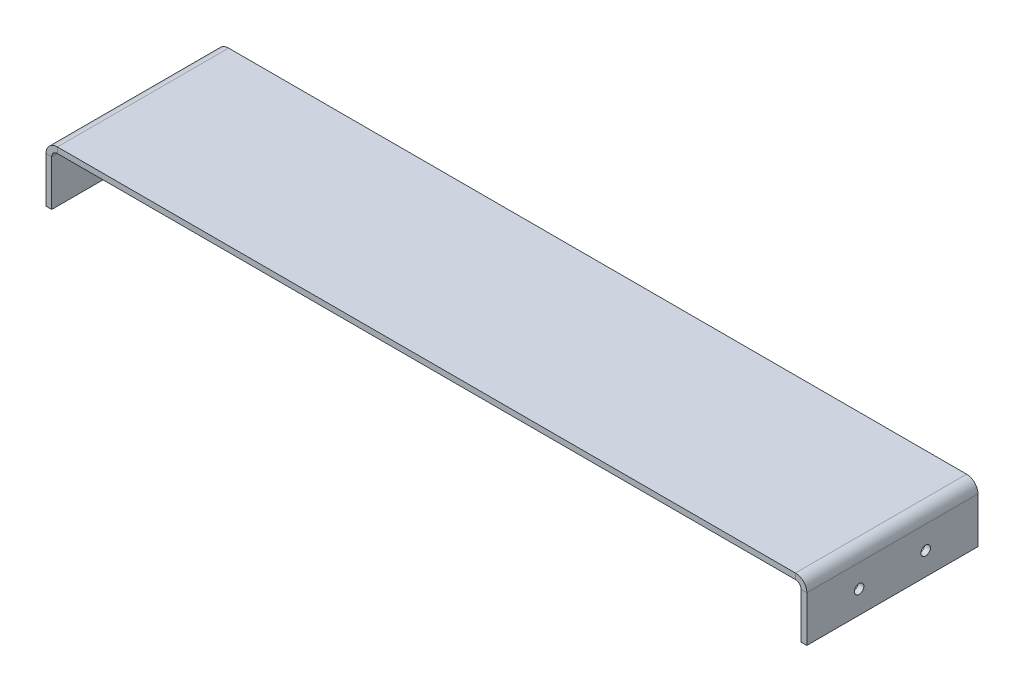
SolidWorks part; units mm, degrees
note: The reader was unsure of these and kept them because the rebuilt part matched: thickness of "Base-Flange1", "Edge-Flange1", "Sheet-Metal2", "Sheet-Metal3", "Sheet-Metal4"; flange length of "Edge-Flange1".
material "Wrought Stainless Steel"
ref_plane "Front Plane" through (0, 0, 0) normal (0, 0, 1) x (1, 0, 0)
ref_plane "Top Plane" through (0, 0, 0) normal (0, 1, 0) x (1, 0, 0)
ref_plane "Right Plane" through (0, 0, 0) normal (1, 0, 0) x (0, 0, -1)
sketch "Sketch1" plane through (0, 0, 0) normal (0, 1, 0) x (1, 0, 0)
  line L0 (0, -1000) -> (0, 49000) construction
  line L1 (-1000, 0) -> (-200, 0) construction
  line L4 (-200, 0) -> (-200, 90)
  line L5 (-200, 90) -> (200, 90)
  line L6 (200, 0) -> (200, 90)
  line L10 (200, 0) -> (49000, 0) construction
  line L11 (-200, 0) -> (200, 0)
  point P16 (0, 23.33)
  dimension "D2" = 90
  dimension "D3" = 400
base flange "Base-Flange1" sketch "Sketch1" thickness 3 reverse thickness direction no parameters "D1"=1
edge flange "Edge-Flange1" sketch "Sketch10" flange profiles "Sketch10", "Sketch11" flange angle 90 flange length 30 flange position material inside bend radius 3 thickness 3 relief obround parameters "D6"=10, "D8"=0.2
sketch "Sketch10" plane through (-200, -3, 0) normal (-1, 0, 0) x (0, 0, -1)
  line L0 (90, 0) -> (0, 0) construction
  line L1 (90, 0) -> (0, 0)
  line L2 (0, 0) -> (0, 27)
  line L3 (0, 27) -> (90, 27)
  line L4 (90, 27) -> (90, 0)
sketch "Sketch11" plane through (200, -3, 0) normal (1, 0, 0) x (0, 0, 1)
  line L0 (0, 0) -> (-90, 0) construction
  line L1 (0, 0) -> (-90, 0)
  line L2 (-90, 0) -> (-90, 27)
  line L3 (-90, 27) -> (0, 27)
  line L4 (0, 27) -> (0, 0)
bend "EdgeBend1" bend radius 3 bend angle 90 parameters "D5"=1
bend "EdgeBend2" bend radius 3 bend angle 90 parameters "D5"=2
sketch "Sketch12" plane through (200, 0, 0) normal (1, 0, 0) x (0, 0, -1)
  line L0 (45, -1030) -> (45, 48970) construction
  line L1 (0, -30) -> (90, -30) construction
  line L2 (-1000, -18) -> (49000, -18) construction
  line L3 (0, -6) -> (0, -30) construction
  circle A0 centre (62.5, -18) radius 2.5
  circle A2 centre (27.5, -18) radius 2.5
  point P5 (45, -30)
  point P10 (0, -18)
  dimension "D2" = 5
  dimension "D1" = 17.5
extrude "Cut-Extrude1" cut sketch "Sketch12" against normal through all normal cut yes
sketch "Bend-Lines1" [suppressed] plane through (0, 0, 0) normal (0, 1, 0) x (1, 0, 0)
sketch "Bounding-Box1" [suppressed] plane through (0, 0, 0) normal (0, 1, 0) x (1, 0, 0)
sheet metal parameters "Sheet-Metal2" thickness 3 parameters "D1"=1, "D7"=5
flat pattern "Flat-Pattern2" [suppressed]
sketch "Bend-Lines2" plane through (0, 0, 0) normal (0, 1, 0) x (1, 0, 0)
sketch3d "Bounding-Box2" [suppressed]
  line L0 (200, 0, 0) -> (-200, 0, 0) construction
  line L1 (200, 70, 0) -> (-200, 70, 0) construction
  line L2 (200, 0, 0) -> (200, 70, 0) construction
  line L3 (-200, 0, 0) -> (-200, 70, 0) construction
sheet metal parameters "Sheet-Metal3" thickness 3 parameters "D1"=1, "D7"=5
flat pattern "Flat-Pattern2"
sketch "Bend-Lines2" plane through (0, 0, 0) normal (0, 1, 0) x (1, 0, 0)
  line L0 (197.5343, 3) -> (197.5343, 70) construction
  line L1 (-197.5343, 70) -> (-197.5343, 3) construction
  line L2 (197.5343, 3) -> (197.5343, 70) construction
  line L3 (-197.5343, 70) -> (-197.5343, 3) construction
sketch3d "Bounding-Box2" [suppressed]
  line L0 (225.0686, 0, 0) -> (-225.0686, 0, 0) construction
  line L1 (225.0686, 70, 0) -> (-225.0686, 70, 0) construction
  line L2 (225.0686, 0, 0) -> (225.0686, 70, 0) construction
  line L3 (-225.0686, 0, 0) -> (-225.0686, 70, 0) construction
bend of the flat pattern "Flatten-<EdgeBend1>1"
bend of the flat pattern "Flatten-<EdgeBend2>1"
sheet metal parameters "Sheet-Metal4" thickness 3 parameters "D1"=1, "D7"=5
flat pattern "Flat-Pattern2"
sketch "Bend-Lines2" plane through (0, 0, 0) normal (0, 1, 0) x (1, 0, 0)
  line L0 (197.5343, 0) -> (197.5343, 90) construction
  line L1 (-197.5343, 90) -> (-197.5343, 0) construction
  line L2 (197.5343, 0) -> (197.5343, 90) construction
  line L3 (-197.5343, 90) -> (-197.5343, 0) construction
sketch3d "Bounding-Box2" [suppressed]
  line L0 (225.0686, 0, 0) -> (-225.0686, 0, 0) construction
  line L1 (225.0686, 90, 0) -> (-225.0686, 90, 0) construction
  line L2 (225.0686, 0, 0) -> (225.0686, 90, 0) construction
  line L3 (-225.0686, 0, 0) -> (-225.0686, 90, 0) construction
bend of the flat pattern "Flatten-<EdgeBend1>1"
bend of the flat pattern "Flatten-<EdgeBend2>1"
